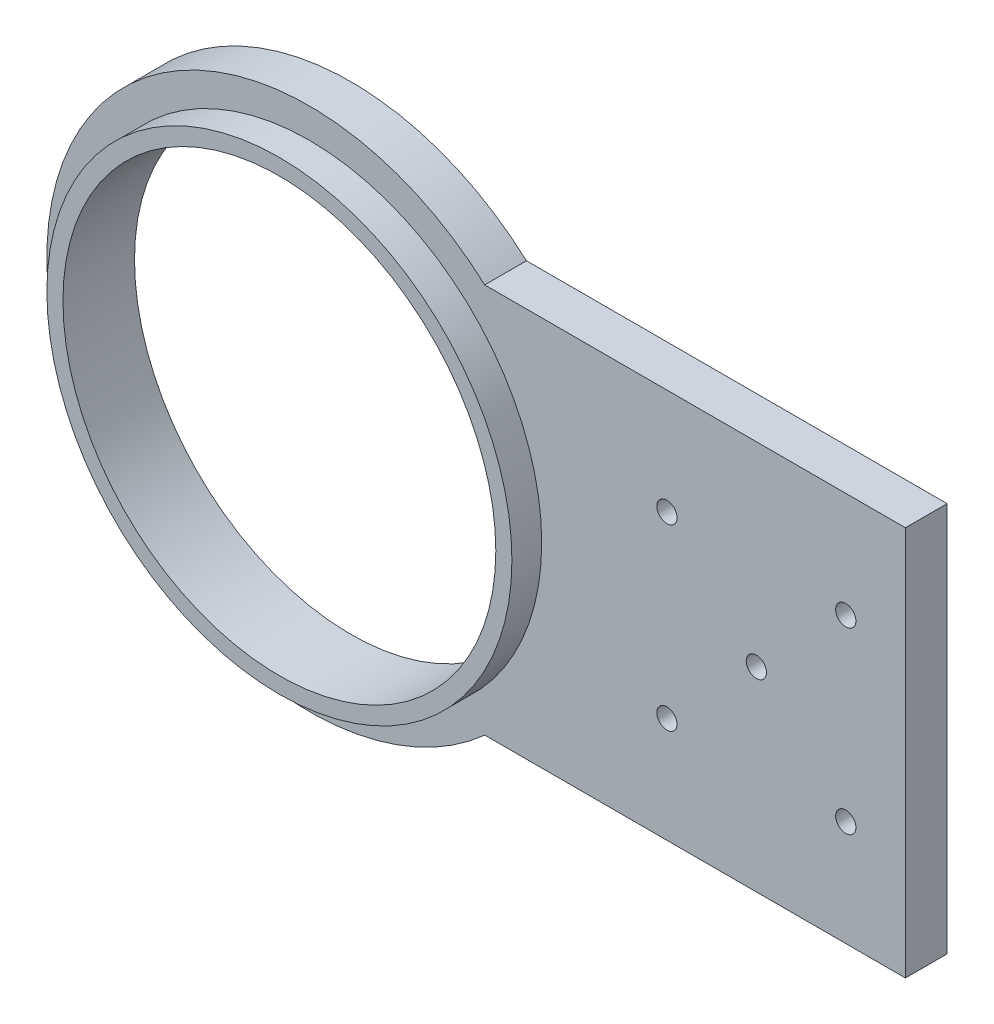
SolidWorks part; units mm, degrees
material "7075-O (SS)"
ref_plane "Front" through (0, 0, 0) normal (0, 0, 1) x (1, 0, 0)
ref_plane "Top" through (0, 0, 0) normal (0, 1, 0) x (1, 0, 0)
ref_plane "Right" through (0, 0, 0) normal (1, 0, 0) x (0, 0, -1)
sketch "Croquis1" plane through (0, 0, 0) normal (0, 0, 1) x (1, 0, 0)
  circle A0 centre (0, 0) radius 36.3
  circle A1 centre (0, 0) radius 39
  dimension "D1" = 72.6
  dimension "D2" = 78
extrude "Saliente-Extruir1" add sketch "Croquis1" along normal mid plane 5
sketch "Croquis2" plane through (0, 0, -2.5) normal (0, 0, -1) x (-1, 0, 0)
  circle A0 centre (0, 0) radius 44
  circle A1 centre (0, 0) radius 36.3 construction
  circle A2 centre (0, 0) radius 36.3
  dimension "D1" = 88
extrude "Saliente-Extruir2" add sketch "Croquis2" along normal blind 7
sketch "Croquis3" plane through (0, 0, -9.5) normal (0, 0, -1) x (-1, 0, 0)
  line L0 (-29.4399, 32.7) -> (-100, 32.7)
  line L1 (-100, 32.7) -> (-100, -32.7)
  line L2 (-100, -32.7) -> (-29.4399, -32.7)
  line L3 (6.6, 0) -> (-6.6, 0) construction
  line L4 (0, 6.6) -> (0, -6.6) construction
  circle A0 centre (0, 0) radius 44 construction
  arc A1 (-29.4399, 32.7) -> (-29.4399, -32.7) centre (0, 0) ccw
  point P10 (-100, 0)
  circle M3 centre (0, 0) radius 44
  dimension "D1" = 65.4
  dimension "D2" = 100
extrude "Saliente-Extruir3" add sketch "Croquis3" against normal blind 7 contours L1 L2 L0 M3 region at (69.6148, 0, -9.5)
hole_wizard "Refrentado para tornillo con cabeza troncocónica de M31" positions "Croquis4" profile "Croquis6" counterbore size "M3" standard "Ansi Metric" end condition up to next
sketch "Croquis4" plane through (0, 0, -9.5) normal (0, 0, -1) x (-1, 0, 0)
  line L1 (-60, -15) -> (-90, -15) construction
  line L2 (-60, -15) -> (-60, 15) construction
  line L3 (-60, 15) -> (-90, 15) construction
  line L4 (-90, -15) -> (-90, 15) construction
  line L5 (-60, -15) -> (-90, 15) construction
  line L6 (-60, 15) -> (-90, -15) construction
  line L7 (6.6, 0) -> (-6.6, 0) construction
  line L8 (-100, 32.7) -> (-100, -32.7) construction
  point P1 (-75, 0)
  point P2 (-90, 15)
  point P29 (-60, -15)
  point P30 (-60, 15)
  point P31 (-90, -15)
  dimension "D1" = 30
  dimension "D2" = 25
sketch "Croquis6" plane through (75, 0, -9.5) normal (1, 0, 0) x (0, 1, 0)
  line L0 (0, 0) -> (0, 7)
  line L1 (0, 7) -> (1.7, 7)
  line L3 (1.7, 7) -> (1.7, 2.4)
  line L4 (1.7, 2.4) -> (3.5, 2.4)
  line L5 (3.5, 2.4) -> (3.5, 0)
  line L7 (3.5, 0) -> (0, 0)
  line L11 (0, -6.35) -> (0, 107.95) construction
  dimension "Diámetro de taladro hasta el siguiente" = 3.4
  dimension "Profundidad de taladro hasta el siguiente" = 7
  dimension "Diámetro de refrentado" = 7
  dimension "Profundidad de refrentado" = 2.4
